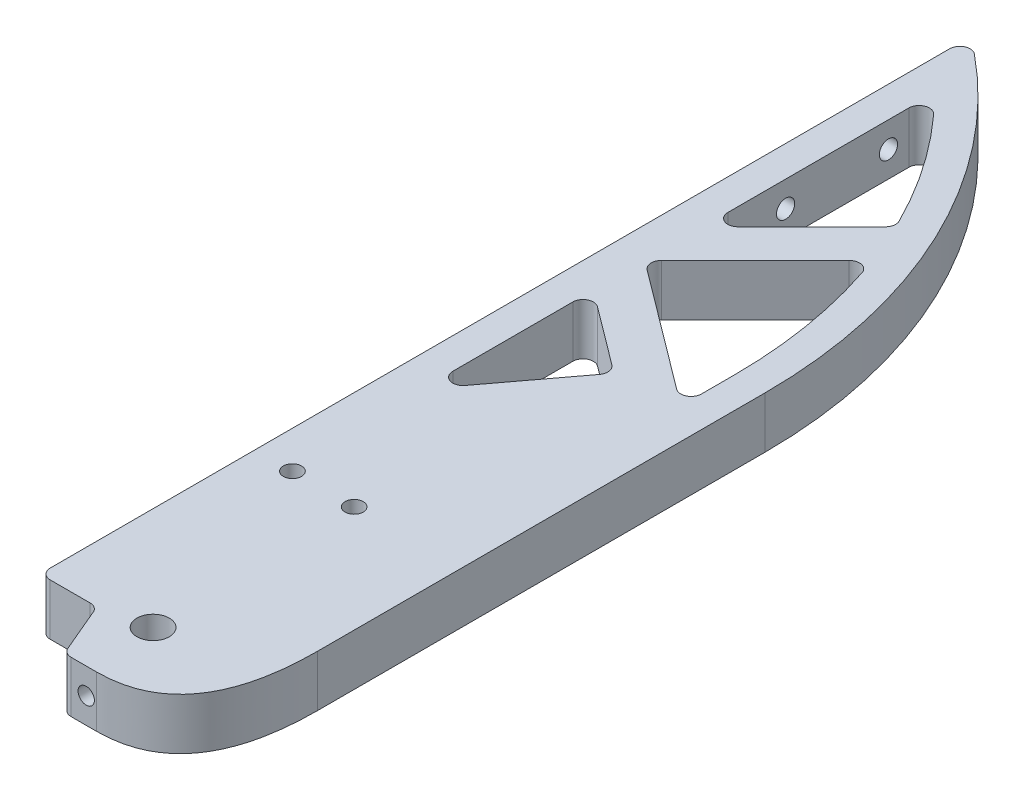
SolidWorks part; units mm, degrees
ref_plane "Front Plane" through (0, 0, 0) normal (0, 0, 1) x (1, 0, 0)
ref_plane "Top Plane" through (0, 0, 0) normal (0, 1, 0) x (1, 0, 0)
ref_plane "Right Plane" through (0, 0, 0) normal (1, 0, 0) x (0, 0, -1)
sketch "Sketch1" plane through (0, 0, 0) normal (0, 1, 0) x (1, 0, 0)
  line L1 (-25.4, -121.92) -> (25.4, -121.92)
  line L2 (-25.4, -121.92) -> (-25.4, 121.92)
  line L3 (-25.4, 121.92) -> (25.4, 121.92)
  line L4 (25.4, -121.92) -> (25.4, 121.92)
  line L5 (-25.4, -121.92) -> (25.4, 121.92) construction
  line L6 (-25.4, 121.92) -> (25.4, -121.92) construction
  point P0 (0, 0)
  dimension "D1" = 243.84
  dimension "D2" = 50.8
extrude "Boss-Extrude1" add sketch "Sketch1" along normal mid plane 12.7
sketch "Sketch2" plane through (0, 6.35, 0) normal (0, 1, 0) x (1, 0, 0)
  line L0 (0, 121.92) -> (0, -121.92) construction
  line L1 (25.4, 121.92) -> (-25.4, 121.92) construction
  line L2 (-25.4, -121.92) -> (25.4, -121.92) construction
  circle A0 centre (0, -105.41) radius 4
  dimension "D1" = 8
  dimension "D2" = 16.51
extrude "Pivot Point" cut sketch "Sketch2" against normal through all
sketch "Sketch3" plane through (0, 6.35, 0) normal (0, 1, 0) x (1, 0, 0)
  line L0 (0, -105.41) -> (0, -113.03) construction
  line L1 (0, -113.03) -> (-25.4, -113.03) construction
  line L2 (-25.4, 121.92) -> (-25.4, -121.92) construction
  line L3 (-25.4, -113.03) -> (-11.176, -113.03) construction
  line L4 (-11.176, -113.03) -> (-11.176, -121.92) construction
  line L5 (-25.4, -121.92) -> (25.4, -121.92) construction
  line L6 (-25.4, -107.95) -> (-9.8374, -107.95)
  line L7 (-9.8374, -107.95) -> (0, -105.41) construction
  line L8 (-6.7202, -113.03) -> (-2.9466, -121.92) construction
  line L10 (-25.4, -88.9) -> (-17.78, -88.9)
  line L11 (-17.78, -88.9) -> (-25.4, -25.4)
  line L12 (-25.4, -25.4) -> (-25.4, 121.92)
  line L13 (-25.4, 121.92) -> (25.4, 121.92)
  line L14 (25.4, 121.92) -> (25.4, 20.32)
  line L15 (25.4, -121.92) -> (25.4, 121.92) construction
  line L16 (25.4, -90.17) -> (25.4, -121.92)
  line L17 (25.4, -121.92) -> (2.54, -121.92)
  line L18 (-2.9466, -121.92) -> (-25.4, -121.92) construction
  line L19 (-25.4, -121.92) -> (-25.4, -25.4)
  line L21 (-11.3324, -107.95) -> (-5.4025, -121.92)
  line L22 (-5.4025, -121.92) -> (-25.4, -121.92)
  line L23 (-25.4, -25.4) -> (-25.4, -88.9)
  circle A0 centre (0, -105.41) radius 10.16 construction
  arc A1 (-9.8374, -107.95) -> (-6.7202, -113.03) centre (0, -105.41) ccw
  arc A2 (-25.4, 121.92) -> (25.4, 20.32) centre (-101.6, 20.32) cw
  spline S0 degree 2 poles (2.54, -121.92) (25.4, -121.92) (25.4, -90.17) knots 0 0 0 1 1 1
  line M22 (-25.4, 121.92) -> (-25.4, -121.92)
  line M23 (-25.4, -121.92) -> (25.4, -121.92)
  dimension "D1" = 7.62
  dimension "D4" = 20.32
  dimension "D6" = 7.62
  dimension "D7" = 63.5
  dimension "D9" = 31.75
  dimension "D10" = 22.86
  dimension "D11" = 101.6
  dimension "D12" = 2.2606
  dimension "D2" = 11.176
  dimension "D3" = 5.08
  dimension "D5" = 113
  dimension "D8" = 19.05
extrude "Main Shape" cut sketch "Sketch3" against normal through all contours A1 L6 L8 M22 M23 | S0 L16 L17 | A2 L14 L13 region at (-16.7977, 6.35, 115.3403)
sketch "Sketch12" plane through (-25.4, 0, 0) normal (-1, 0, 0) x (0, 0, 1)
  line L0 (-93.98, 0) -> (-68.58, 0)
  line L1 (-121.92, 6.35) -> (-121.92, -6.35) construction
  point P0 (-93.98, 0)
  point P2 (-68.58, 0)
  point P9 (-121.92, 0)
  dimension "D1" = 25.4
  dimension "D2" = 27.94
sketch "Sketch4" plane through (0, 6.35, 0) normal (0, 1, 0) x (1, 0, 0)
  line L0 (-17.78, 105.3247) -> (-17.78, 48.1747)
  line L1 (-17.78, 48.1747) -> (6.0241, 71.9788)
  line L2 (10.3072, 61.8935) -> (-17.78, 33.8062)
  line L3 (-17.78, 33.8062) -> (17.78, 7.1362)
  line L4 (17.78, 7.1362) -> (17.78, 20.32)
  line L5 (-17.78, 21.1062) -> (2.54, 5.8662)
  line L7 (-17.78, -21.2271) -> (-17.78, 21.1062)
  line L9 (2.54, 5.8662) -> (-17.78, -21.2271)
  line L32 (17.78, -90.17) -> (17.78, 20.32)
  line L33 (-17.78, 105.3247) -> (-17.78, -100.33)
  line L37 (-17.78, -100.33) -> (-6.2888, -100.33)
  line L38 (-6.2888, -100.33) -> (-0.3589, -114.3)
  line L39 (-0.3589, -114.3) -> (2.54, -114.3)
  line L40 (17.78, -90.17) -> (17.78, 20.32) construction
  line L41 (-17.78, 105.3247) -> (-17.78, -21.2271) construction
  line L45 (-17.78, -100.33) -> (-6.2888, -100.33) construction
  line L46 (-6.2888, -100.33) -> (-0.3589, -114.3) construction
  line L47 (-0.3589, -114.3) -> (2.54, -114.3) construction
  arc A0 (-17.78, 105.3247) -> (6.0241, 71.9788) centre (-101.6, 20.32) cw
  arc A1 (10.3072, 61.8935) -> (17.78, 20.32) centre (-101.6, 20.32) cw
  arc A4 (17.78, 20.32) -> (-17.78, 105.3247) centre (-101.6, 20.32) ccw
  arc A5 (17.78, 20.32) -> (-17.78, 105.3247) centre (-101.6, 20.32) ccw construction
  spline S0 degree 3 poles (182.3768, -3106.4872) (-121.3578, 113.6597) (-43.6576, -124.5249) (6.9357, -113.8408) (7.2696, -113.7586) (7.9257, -113.5702) (8.8946, -113.2517) (9.8134, -112.8132) (10.6914, -112.2772) (10.9756, -112.0829) (11.5168, -111.6709) (11.7754, -111.4522) (12.5172, -110.76) (12.967, -110.2498) (13.7869, -109.1494) (14.1472, -108.5738) (14.7943, -107.3847) (15.0809, -106.7713) (15.5964, -105.5147) (15.8257, -104.8691) (16.2318, -103.5721) (16.4093, -102.9189) (16.8809, -100.9486) (17.1147, -99.6205) (17.47, -96.9442) (17.5908, -95.5951) (23.2835, 3.8327) (-199.485, 108.5636) (3001.6783, 113.4716) knots -4.573947 -4.573947 -4.573947 -4.573947 0.125 0.125 0.15625 0.15625 0.1875 0.25 0.25 0.28125 0.28125 0.3125 0.3125 0.375 0.375 0.4375 0.4375 0.5 0.5 0.5625 0.5625 0.625 0.625 0.75 0.75 0.875 0.875 9.919668 9.919668 9.919668 9.919668 only from (2.54, -114.3) to (17.78, -90.17)
  spline S1 degree 3 poles (2.54, -114.3) (3.9081, -114.3) (5.2645, -114.1937) (6.9357, -113.8408) (7.2696, -113.7586) (7.9257, -113.5702) (8.8946, -113.2517) (9.8134, -112.8132) (10.6914, -112.2772) (10.9756, -112.0829) (11.5168, -111.6709) (11.7754, -111.4522) (12.5172, -110.76) (12.967, -110.2498) (13.7869, -109.1494) (14.1472, -108.5738) (14.7943, -107.3847) (15.0809, -106.7713) (15.5964, -105.5147) (15.8257, -104.8691) (16.2318, -103.5721) (16.4093, -102.9189) (16.8809, -100.9486) (17.1147, -99.6205) (17.47, -96.9442) (17.5908, -95.5951) (17.746, -92.8843) (17.78, -91.5277) (17.78, -90.17) knots 0 0 0 0 0.125 0.125 0.15625 0.15625 0.1875 0.25 0.25 0.28125 0.28125 0.3125 0.3125 0.375 0.375 0.4375 0.4375 0.5 0.5 0.5625 0.5625 0.625 0.625 0.75 0.75 0.875 0.875 1 1 1 1 construction
  dimension "D2" = 119.38
  dimension "D3" = 45
  dimension "D4" = 57.15
  dimension "D5" = 10.16
  dimension "D6" = 44.45
  dimension "D7" = 25.4
  dimension "D8" = 10.16
  dimension "D1" = 7.62
extrude "Optimizing Weight Cutout" cut sketch "Sketch4" against normal through all contours A1 L2 L3 L4 | L7 L5 | L1 A0 L0 region at (4.6512, 6.35, -34.4305) region at (-11.0067, 6.35, -1.9151)
hole_wizard "#8 Clearance Hole1" positions "Sketch12" profile "Sketch11" hole size "#8" standard "ANSI Inch" end condition up to next
sketch "Sketch11" plane through (-25.4, 0, -93.98) normal (0, 1, 0) x (0, 0, 1)
  line L0 (0, 0) -> (0, 27.2563)
  line L1 (0, 27.2563) -> (2.2479, 27.2563)
  line L2 (2.2479, 27.2563) -> (2.2479, 0)
  line L5 (2.2479, 0) -> (0, 0)
  line L11 (0, -6.35) -> (0, 107.95) construction
  dimension "Thru Hole Dia." = 4.4958
  dimension "Thru Hole Depth" = 27.2563
sketch "Sketch7" plane through (0, 0, 121.92) normal (0, 0, 1) x (1, 0, 0)
  point P0 (0, 0)
hole_wizard "#10-32 Tapped Hole1" positions "Sketch7" profile "Sketch8" tap size "#10-32" standard "ANSI Inch"
sketch "Sketch8" plane through (0, 0, 121.92) normal (1, 0, 0) x (0, -1, 0)
  line L0 (0, 0) -> (0, 15.1833)
  line L1 (0, 15.1833) -> (2.0193, 13.97)
  line L2 (2.0193, 13.97) -> (2.0193, 0)
  line L5 (2.0193, 0) -> (0, 0)
  line L10 (0, 15.1833) -> (-2.0193, 13.97) construction
  line L11 (0, -6.35) -> (0, 107.95) construction
  dimension "Tap Drill Dia." = 4.0386
  dimension "Tap Drill Depth" = 13.97
  dimension "Drill Angle" = 118
cosmetic thread "Hole Thread1" parameters "D1"=9.652, "D2"=4.826
sketch "Set Screw Ref" plane through (0, 6.35, 0) normal (0, 1, 0) x (1, 0, 0)
  line L0 (0, -105.41) -> (0, -121.92) construction
  line L1 (-5.4025, -121.92) -> (2.54, -121.92) construction
  line L2 (0, -121.92) -> (0, -107.505)
  line L3 (0, -109.41) -> (1.778, -109.41)
  circle A0 centre (0, -105.41) radius 4 construction
  dimension "D1" = 1.905
  dimension "D2" = 1.778
fillet "Fillet1" radius 2.54 13 edges at (-25.4, 0, 107.95) (-5.4025, 0, 121.92) (-25.4, 0, -121.92) (-17.78, 0, -105.3247) (-17.78, 0, -48.1747) (6.0241, 0, -71.9788) (10.3072, 0, -61.8935) (-17.78, 0, -21.1062) (17.78, 0, -7.1362) (-17.78, 0, -33.8062) (-11.3324, 0, 107.95) (2.54, 0, -5.8662) (-17.78, 0, 21.2271)
sketch "Sketch15" plane through (0, 6.35, 0) normal (0, 1, 0) x (1, 0, 0)
  line L0 (-16.2052, -54.7915) -> (-0.9652, -54.7915)
  line L3 (25.4, -90.17) -> (25.4, 20.32) construction
  point P67 (-16.2052, -54.7915)
  point P70 (-0.9652, -54.7915)
  dimension "D1" = 15.24
  dimension "D2" = 54.8
  dimension "D3" = 26.3652
hole_wizard "#8 Clearance Hole2" positions "Sketch15" profile "Sketch14" hole size "#8" standard "ANSI Inch" end condition through all
sketch "Sketch14" plane through (-16.2052, 6.35, 54.7915) normal (1, 0, 0) x (0, 0, 1)
  line L0 (0, 0) -> (0, 12.7)
  line L1 (0, 12.7) -> (2.2479, 12.7)
  line L2 (2.2479, 12.7) -> (2.2479, 0)
  line L5 (2.2479, 0) -> (0, 0)
  line L11 (0, -6.35) -> (0, 107.95) construction
  dimension "Thru Hole Dia." = 4.4958
  dimension "Thru Hole Depth" = 12.7
